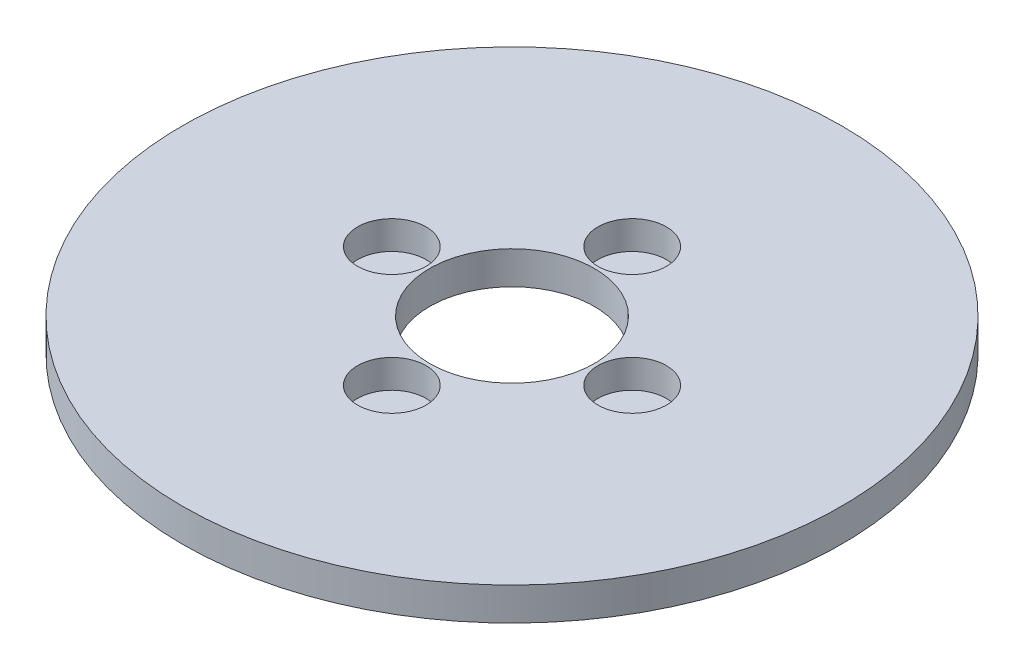
SolidWorks part; units mm, degrees
ref_plane "Front Plane" through (0, 0, 0) normal (0, 0, 1) x (1, 0, 0)
ref_plane "Top Plane" through (0, 0, 0) normal (0, 1, 0) x (1, 0, 0)
ref_plane "Right Plane" through (0, 0, 0) normal (1, 0, 0) x (0, 0, -1)
sketch "Sketch1" plane through (0, 0, 0) normal (0, 1, 0) x (1, 0, 0)
  circle A0 centre (0, 0) radius 40
  dimension "FLANGE_OD" = 80
extrude "Boss-Extrude1" add sketch "Sketch1" along normal blind 4
sketch "Sketch2" plane through (0, 0, 0) normal (0, 1, 0) x (1, 0, 0)
  circle A0 centre (0, 0) radius 10
  dimension "BORE_D" = 20
extrude "Cut-Extrude1" cut sketch "Sketch2" along normal through all
sketch "Sketch3" plane through (0, 4, 0) normal (0, 1, 0) x (1, 0, 0)
  circle A0 centre (0, 0) radius 14.5875 construction
  circle A1 centre (-14.5875, 0) radius 4.1563
  dimension "BOLT_D" = 8.3126
  dimension "BOLT_PCD" = 29.175
extrude "Cut-Extrude2" cut sketch "Sketch3" against normal blind 3.4497
pattern_circular "CirPattern1" count 4 over 360 about axis through (0, 0, 0) along (0, 1, 0) of "Cut-Extrude2"
